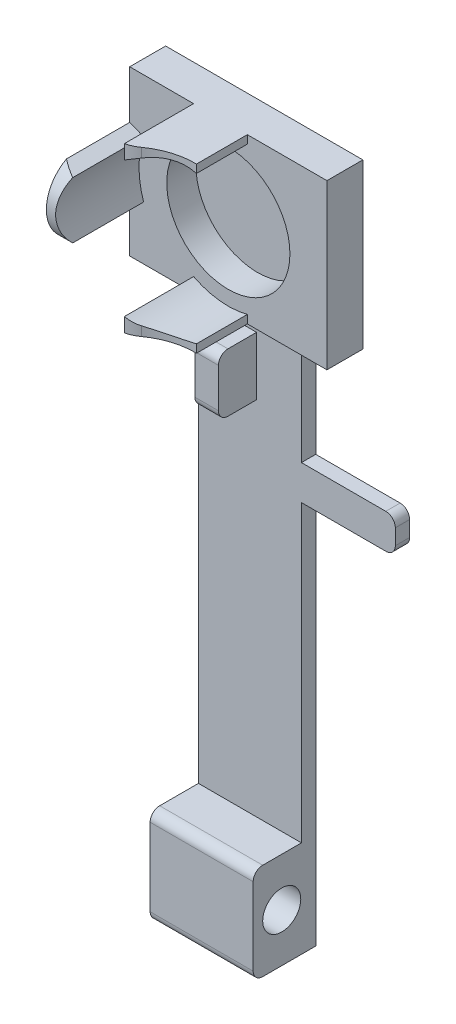
SolidWorks part; units mm, degrees
ref_plane "前视基准面" through (0, 0, 0) normal (0, 0, 1) x (1, 0, 0)
ref_plane "上视基准面" through (0, 0, 0) normal (0, 1, 0) x (1, 0, 0)
ref_plane "右视基准面" through (0, 0, 0) normal (1, 0, 0) x (0, 0, -1)
sketch "草图1" plane through (0, 0, 0) normal (0, 0, 1) x (1, 0, 0)
  line L0 (-49.5626, 0) -> (87.9237, 0) construction
  line L1 (0, 61.0709) -> (0, -78.2567) construction
  line L2 (10.82, -17.215) -> (10.82, -41.305)
  line L3 (20.715, -17.215) -> (10.82, -17.215)
  line L4 (20.715, -17.215) -> (20.715, 17.215)
  line L5 (20.715, 17.215) -> (-20.715, 17.215)
  line L6 (-20.715, -17.215) -> (-20.715, 17.215)
  line L7 (20.715, -17.215) -> (-20.715, 17.215) construction
  line L8 (20.715, 17.215) -> (-20.715, -17.215) construction
  line L9 (10.82, -41.305) -> (28.54, -41.305)
  line L10 (30.54, -43.305) -> (30.54, -46.575)
  line L11 (28.54, -48.575) -> (10.82, -48.575)
  line L12 (10.82, -48.575) -> (10.82, -130.765)
  line L13 (10.82, -130.765) -> (-10.82, -130.765)
  line L14 (-10.82, -130.765) -> (-10.82, -17.215)
  line L15 (-10.82, -17.215) -> (-20.715, -17.215)
  arc A0 (30.54, -46.575) -> (28.54, -48.575) centre (28.54, -46.575) cw
  arc A1 (30.54, -43.305) -> (28.54, -41.305) centre (28.54, -43.305) ccw
  point P5 (0, 0)
  point P27 (30.54, -48.575)
  point P30 (30.54, -41.305)
  dimension "D8" = 2
  dimension "D1" = 41.43
  dimension "D2" = 34.43
  dimension "D3" = 24.09
  dimension "D4" = 19.72
  dimension "D5" = 7.27
  dimension "D6" = 82.19
  dimension "D7" = 21.64
extrude "凸台-拉伸4" add sketch "草图1" along normal blind 3.01 contours L6 L5 L4 L3 L2 L9 A1 L10 A0 L11 L12 L13 L14 L15
sketch "草图3" plane through (0, 0, 3.01) normal (0, 0, 1) x (1, 0, 0)
  line L0 (-20.715, -17.215) -> (20.715, -17.215)
  line L1 (20.715, -17.215) -> (20.715, 17.215)
  line L2 (20.715, -17.215) -> (20.715, 17.215) construction
  line L3 (20.715, 17.215) -> (-20.715, 17.215)
  line L4 (-20.715, 17.215) -> (-20.715, -17.215)
extrude "凸台-拉伸5" add sketch "草图3" along normal blind 4.54
sketch "草图4" plane through (0, 0, 7.55) normal (0, 0, 1) x (1, 0, 0)
  circle A0 centre (0, 0) radius 12.94
  dimension "D1" = 25.88
extrude "切除-拉伸1" cut sketch "草图4" against normal blind 6.14
ref_plane "基准面5" through (-3.55, 0, 0) normal (-1, 0, 0) x (0, 0, 1)
sketch "草图6" plane through (-3.55, 0, 0) normal (-1, 0, 0) x (0, 0, 1)
  line L0 (3.01, -17.5318) -> (3.01, -71.3401) construction
  line L1 (3.01, -22.315) -> (9.02, -22.315)
  line L2 (3.01, -22.315) -> (3.01, -34.585)
  line L3 (3.01, -34.585) -> (9.02, -34.585)
  line L4 (11.02, -24.315) -> (11.02, -32.585)
  line L5 (3.01, -130.765) -> (3.01, -17.215) construction
  arc A0 (9.02, -34.585) -> (11.02, -32.585) centre (9.02, -32.585) ccw
  arc A1 (9.02, -22.315) -> (11.02, -24.315) centre (9.02, -24.315) cw
  point P13 (11.02, -22.315)
  dimension "D4" = 2
  dimension "D1" = 5.1
  dimension "D2" = 12.27
  dimension "D3" = 8.01
extrude "凸台-拉伸7" add sketch "草图6" against normal blind 4.94 contours L1 A1 L4 A0 L3 L2
sketch "草图7" plane through (-10.82, 0, 0) normal (-1, 0, 0) x (0, 0, 1)
  line L0 (3.01, -17.215) -> (3.01, -140.2594) construction
  line L1 (3.01, -17.215) -> (0, -17.215) construction
  line L2 (7.55, -17.215) -> (0, -17.215) construction
  line L3 (0, -130.765) -> (39.0633, -130.765) construction
  line L4 (3.01, -130.765) -> (0, -130.765) construction
  line L5 (3.01, -130.765) -> (3.01, -17.215) construction
  line L6 (3.01, -130.765) -> (11.15, -130.765)
  line L7 (3.01, -130.765) -> (3.01, -110.485)
  line L8 (3.01, -110.485) -> (11.15, -110.485)
  line L9 (13.15, -128.765) -> (13.15, -112.485)
  arc A0 (11.15, -130.765) -> (13.15, -128.765) centre (11.15, -128.765) ccw
  arc A1 (13.15, -112.485) -> (11.15, -110.485) centre (11.15, -112.485) ccw
  point P21 (13.15, -110.485)
  dimension "D3" = 2
  dimension "D1" = 20.28
  dimension "D2" = 10.14
extrude "凸台-拉伸9" add sketch "草图7" against normal up to surface (21.64 mm away) up to face at (10.82, -89.67, 1.505)
sketch "草图8" plane through (-10.82, 0, 0) normal (-1, 0, 0) x (0, 0, 1)
  line L0 (13.15, -128.765) -> (13.15, -112.485) construction
  circle A0 centre (7.15, -120.625) radius 4
  point P4 (13.15, -120.625)
  dimension "D1" = 8
  dimension "D2" = 6
extrude "切除-拉伸2" cut sketch "草图8" against normal through all
sketch "草图9" plane through (0, 0, 7.55) normal (0, 0, 1) x (1, 0, 0)
  line L0 (20.715, 17.215) -> (-20.715, 17.215) construction
  line L1 (3.9942, 17.215) -> (-7.2904, 17.215)
  line L2 (3.9942, 17.215) -> (3.9942, 15.4934)
  line L4 (-7.2904, 17.215) -> (-7.2904, 14.2425)
  arc A0 (3.9942, 15.4934) -> (-7.2904, 14.2425) centre (0, 0) ccw
  dimension "D1" = 32
extrude "凸台-拉伸10" add sketch "草图9" along normal blind 14.55
sketch "草图10" plane through (0, 17.215, 0) normal (0, 1, 0) x (1, 0, 0)
  line L1 (3.9942, -22.1) -> (3.9942, -7.55) construction
  line L2 (3.9942, -18.1677) -> (3.9942, -22.1)
  line L3 (3.9942, -22.1) -> (-7.2904, -22.1)
  line L4 (3.9942, -18.1677) -> (3.9942, -22.1)
  line L5 (3.9942, -18.2322) -> (3.9942, -21.9479)
  line L7 (-7.2904, -22.1) -> (3.9942, -22.1)
  arc A0 (-7.2904, -22.1) -> (-4.7995, -20.9614) centre (-8.9238, -15.2327) ccw
  arc A1 (-4.7995, -20.9614) -> (3.9942, -18.2322) centre (3.6735, -32.7303) cw
  line M8 (-7.2904, -22.1) -> (3.9942, -22.1)
  line M9 (3.9942, -22.1) -> (3.9942, -7.55)
extrude "切除-拉伸7" cut sketch "草图10" against normal up to next contours A1 A0 L4 M8 M9 region at (-0.0021, 17.215, 20.5322)
ref_axis "基准轴1" through (0, 0, 1.41) along (0, 0, 1)
sketch "草图11" plane through (0, 0, 7.55) normal (0, 0, 1) x (1, 0, 0)
  line L0 (0, 0) -> (133.821, 0) construction
  line L1 (0, 0) -> (0, -149.2146) construction
ref_plane "基准面6" through (0, 0, 0) normal (0, -1, 0) x (-1, 0, 0)
mirror "镜向1" about plane through (0, 0, 0) normal (0, -1, 0) of "切除-拉伸7", "凸台-拉伸10"
ref_axis "基准轴3" through (0, 0, 1.41) along (0, 0, 1)
sketch "草图12" plane through (0, 0, 7.55) normal (0, 0, 1) x (1, 0, 0)
  line L0 (-17.8024, 5.9432) -> (-20.715, 7.0951)
  line L2 (-20.715, 17.215) -> (-20.715, -17.215) construction
  line L3 (-17.8024, -5.9432) -> (-20.715, -7.0951)
  line L4 (-73.6016, 0) -> (73.6016, 0) construction
  line L5 (0.6045, 0) -> (-31.9257, 0) construction
  line L6 (0, 0) -> (133.821, 0) construction
  line L7 (-20.715, -7.0951) -> (-20.715, 7.0951)
  arc A1 (-17.8024, 5.9432) -> (-17.8024, -5.9432) centre (0, 0) ccw
extrude "凸台-拉伸11" add sketch "草图12" along normal blind 17.51
sketch "草图13" plane through (-20.715, 0, 0) normal (-1, 0, 0) x (0, 0, 1)
  line L0 (25.06, 7.0951) -> (7.55, 7.0951) construction
  line L1 (25.06, -7.0951) -> (7.55, -7.0951) construction
  line L2 (20.8233, -7.0951) -> (25.06, -7.0951)
  line L3 (25.06, -7.0951) -> (25.06, 7.0951)
  line L4 (25.06, 7.0951) -> (20.8233, 7.0951)
  arc A0 (20.8233, 7.0951) -> (20.8233, -7.0951) centre (17.0006, 0) cw
  line M4 (7.55, -7.0951) -> (25.06, -7.0951)
  line M5 (25.06, -7.0951) -> (25.06, 7.0951)
  line M6 (25.06, 7.0951) -> (7.55, 7.0951)
extrude "切除-拉伸8" cut sketch "草图13" against normal up to next contours A0 M5 M4 | A0 L3 M6 region at (-20.715, -5.4276, 23.8777) region at (-20.715, 5.4276, 23.8777)
